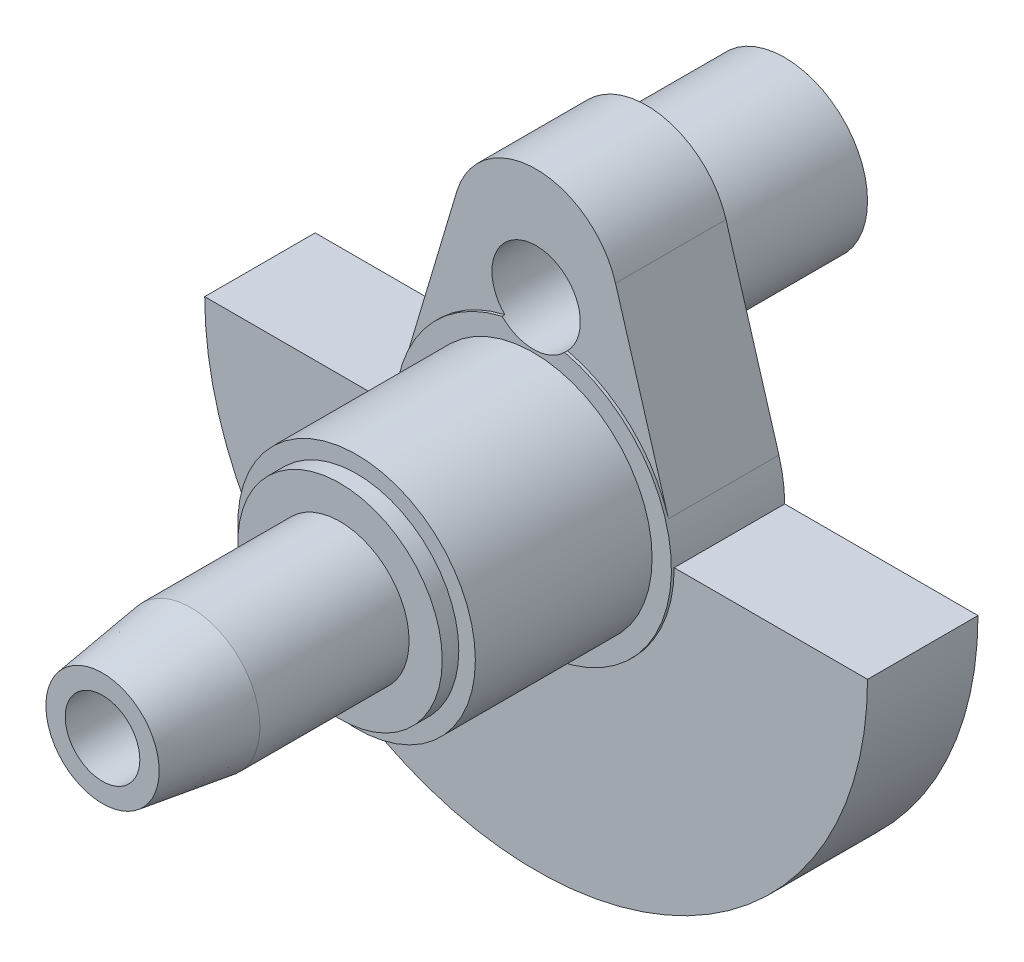
SolidWorks part; units mm, degrees
ref_plane "Front Plane" through (0, 0, 0) normal (0, 0, 1) x (1, 0, 0)
ref_plane "Top Plane" through (0, 0, 0) normal (0, 1, 0) x (1, 0, 0)
ref_plane "Right Plane" through (0, 0, 0) normal (1, 0, 0) x (0, 0, -1)
sketch "Sketch1" plane through (0, 0, 0) normal (0, 0, 1) x (1, 0, 0)
  line L0 (0, 0) -> (0, 70) construction
  line L1 (-28.7494, 78.5714) -> (-47.9157, 14.2857)
  line L2 (28.7494, 78.5714) -> (47.9157, 14.2857)
  line L3 (-41.7399, 35) -> (41.7399, 35) construction
  line L4 (-120, 0) -> (-50, 0)
  line L5 (120, 0) -> (50, 0)
  circle A0 centre (0, 0) radius 50
  arc A1 (-28.7494, 78.5714) -> (28.7494, 78.5714) centre (0, 70) cw
  arc A2 (120, 0) -> (-120, 0) centre (0, 0) cw
  point P10 (0, 35)
  dimension "D1" = 100
  dimension "D2" = 30
  dimension "D4" = 120
  dimension "D3" = 70
extrude "Boss-Extrude1" add sketch "Sketch1" along normal blind 1 and the other way blind 40 contours A0 region at (0, 0, 0)
extrude "Boss-Extrude2" add sketch "Sketch1<3>" against normal up to surface (40 mm away) contours A2 L5 A0 L4 | A1 L1 A0 L2 region at (0, 66.8029, 0) region at (0, -57.171, 0) up to face at (50, 0, -40)
sketch "Sketch1<3>" plane through (0, 0, 0) normal (0, 0, 1) x (1, 0, 0) same geometry as "Sketch1"
sketch "Sketch2" plane through (0, 0, 0) normal (1, 0, 0) x (0, 0, -1)
  line L0 (-1, 0) -> (-1, 43)
  line L1 (-1, 50) -> (-1, -50) construction
  line L2 (-1, 43) -> (-65, 43)
  line L3 (-65, 43) -> (-65, 37)
  line L4 (-65, 37) -> (-71, 37)
  line L5 (-71, 37) -> (-71, 25)
  line L6 (-71, 25) -> (-125, 25)
  line L7 (-125, 25) -> (-125, 0)
  line L8 (-125, 0) -> (-1, 0)
  dimension "D1" = 43
  dimension "D2" = 64
  dimension "D3" = 6
  dimension "D4" = 12
  dimension "D5" = 54
revolve "Revolve1" add sketch "Sketch2" angle 360 about L8
sketch "Sketch3" plane through (0, 0, 125) normal (0, 0, 1) x (1, 0, 0)
  circle A1 centre (0, 0) radius 25
  circle A2 centre (0, 0) radius 25
  dimension "D1" = 0
extrude "Boss-Extrude3" add sketch "Sketch3" along normal blind 32 draft 8
sketch "Sketch4" plane through (0, 0, -40) normal (0, 0, -1) x (-1, 0, 0)
  circle A0 centre (0, 60) radius 30
  arc A2 (28.7494, 78.5714) -> (-28.7494, 78.5714) centre (0, 70) ccw construction
  dimension "D1" = 60
extrude "Boss-Extrude4" add sketch "Sketch4" along normal blind 50
sketch "Sketch5" plane through (0, 0, -90) normal (0, 0, -1) x (-1, 0, 0)
  circle A2 centre (0, 60) radius 21
  circle A3 centre (0, 60) radius 21
  dimension "D1" = 9
extrude "Cut-Extrude1" cut sketch "Sketch5" against normal blind 25
sketch "Sketch6" plane through (0, 0, -65) normal (0, 0, -1) x (-1, 0, 0)
  circle A2 centre (0, 60) radius 11
  circle A3 centre (0, 60) radius 11
  dimension "D1" = 10
extrude "Cut-Extrude2" cut sketch "Sketch6" against normal up to surface (66 mm away) up to face at (50, 0, 1)
sketch "Sketch7" plane through (0, 0, -40) normal (0, 0, -1) x (-1, 0, 0)
  circle A2 centre (0, 60) radius 16
  circle A3 centre (0, 60) radius 16
  dimension "D1" = 5
extrude "Cut-Extrude3" cut sketch "Sketch7" against normal up to surface (41 mm away) up to face at (0, -0.5, 1)
sketch "Sketch8" plane through (0, 0, 157) normal (0, 0, 1) x (1, 0, 0)
  circle A2 centre (0, 0) radius 13.5027
  circle A3 centre (0, 0) radius 13.5027
  dimension "D1" = 7
extrude "Cut-Extrude4" cut sketch "Sketch8" against normal blind 30
equation "\"D2@Sketch1\"=\"D1@Sketch1\"*.3"
equation "\"D3@Sketch1\"=\"D1@Sketch1\"*.7"
equation "\"D4@Sketch1\"=\"D1@Sketch1\"*1.2"
equation "\"D1@Boss-Extrude1\"=\"D1@Sketch1\"*.01"
equation "\"D2@Boss-Extrude1\"=\"D1@Sketch1\"*.4"
